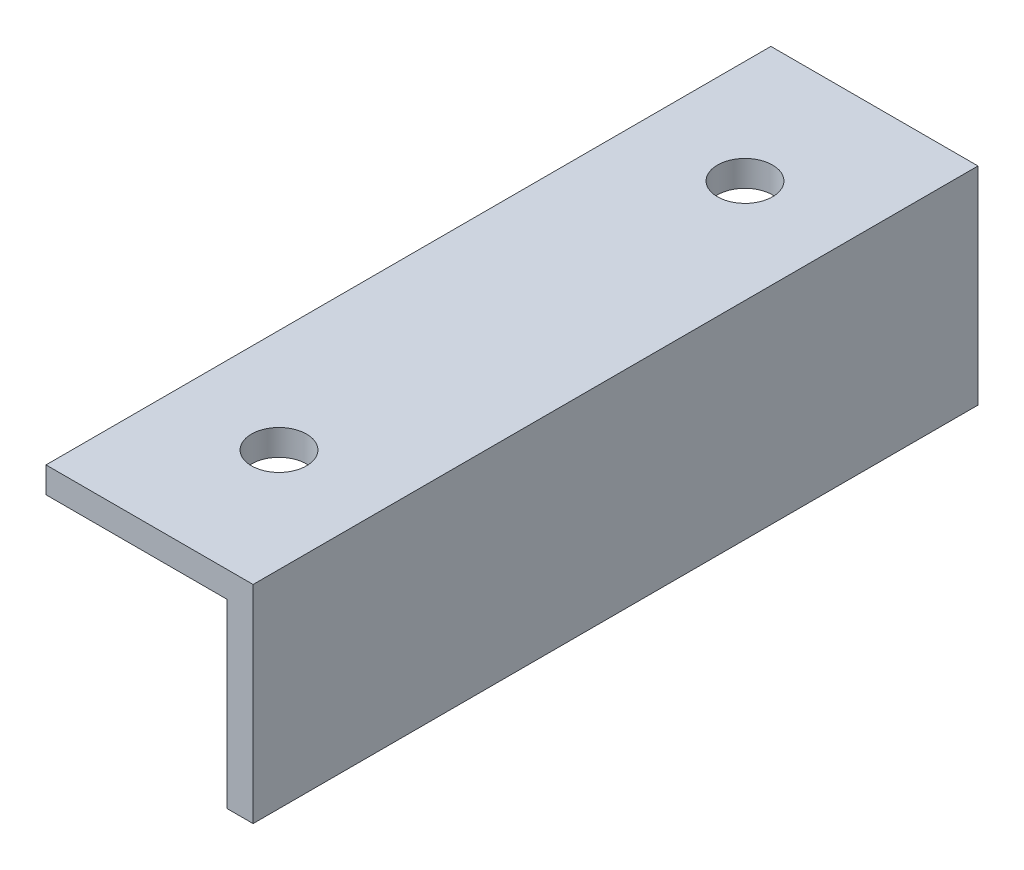
SolidWorks part; units mm, degrees
material "6061 Alloy"
ref_plane "Front" through (0, 0, 0) normal (0, 0, 1) x (1, 0, 0)
ref_plane "Top" through (0, 0, 0) normal (0, 1, 0) x (1, 0, 0)
ref_plane "Right" through (0, 0, 0) normal (1, 0, 0) x (0, 0, -1)
sketch "Sketch1" plane through (0, 0, 0) normal (0, 0, 1) x (1, 0, 0)
  line L0 (0, 0) -> (0, 25.4)
  line L1 (0, 25.4) -> (-25.4, 25.4)
  line L2 (-25.4, 25.4) -> (-25.4, 22.225)
  line L3 (-25.4, 22.225) -> (-3.175, 22.225)
  line L4 (-3.175, 22.225) -> (-3.175, 0)
  line L5 (-3.175, 0) -> (0, 0)
  dimension "D1" = 25.4
  dimension "D2" = 3.175
extrude "Boss-Extrude1" add sketch "Sketch1" along normal blind 88.9
sketch "Sketch2" plane through (0, 25.4, 0) normal (0, 1, 0) x (1, 0, 0)
  line L0 (0, -15.875) -> (-25.4, -15.875) construction
  line L1 (0, -88.9) -> (0, 0) construction
  line L2 (-25.4, -88.9) -> (-25.4, 0) construction
  line L3 (-12.7, -15.875) -> (-12.7, 0) construction
  line L4 (0, 0) -> (-25.4, 0) construction
  line L5 (-12.7, -88.9) -> (-12.7, -73.025) construction
  line L6 (0, -88.9) -> (-25.4, -88.9) construction
  circle A0 centre (-12.7, -15.875) radius 3.3782
  circle A1 centre (-12.7, -73.025) radius 3.3782
  dimension "D1" = 15.875
  dimension "D2" = 6.7564
extrude "Cut-Extrude1" cut sketch "Sketch2" against normal through all
